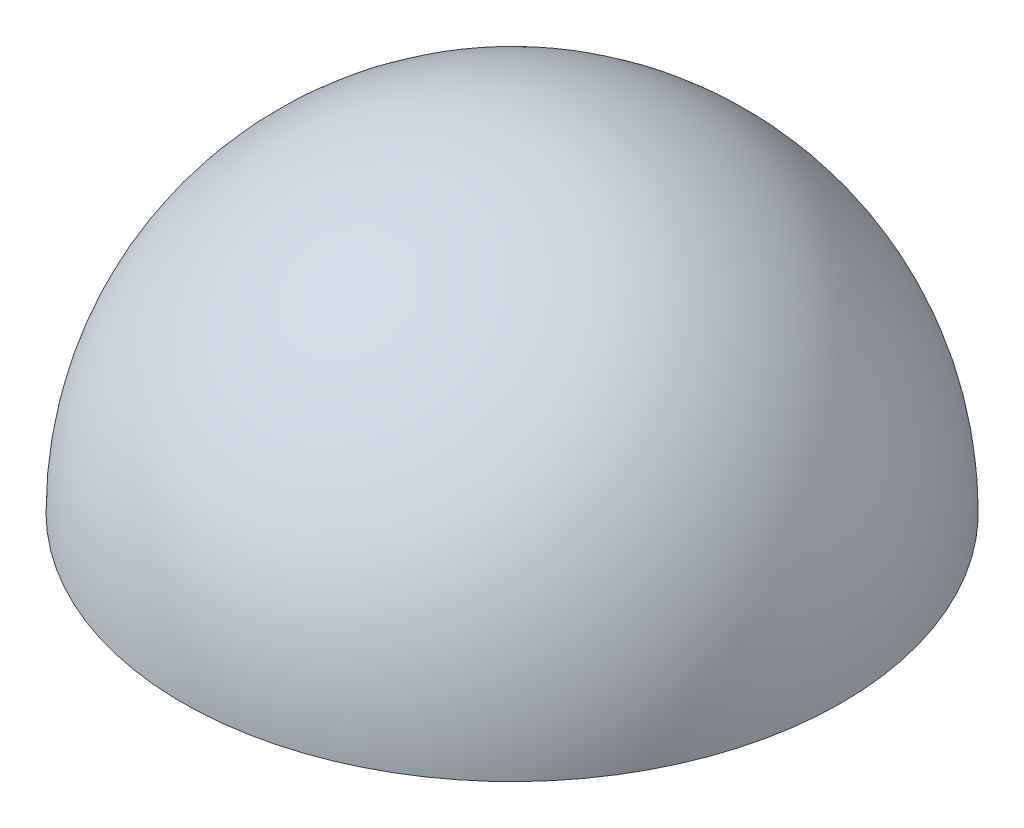
SolidWorks part; units mm, degrees
ref_plane "Front Plane" through (0, 0, 0) normal (0, 0, 1) x (1, 0, 0)
ref_plane "Top Plane" through (0, 0, 0) normal (0, 1, 0) x (1, 0, 0)
ref_plane "Right Plane" through (0, 0, 0) normal (1, 0, 0) x (0, 0, -1)
sketch "Sketch1" plane through (0, 0, 0) normal (0, 1, 0) x (1, 0, 0)
  line L0 (-19.7227, 26.8438) -> (-8.6611, -8.9876)
  circle A0 centre (-14.1919, 8.9281) radius 18.75
  dimension "D1" = 37.5
revolve "Revolve1" add sketch "Sketch1" angle 180 about L0 region at (-21.7955, 0, -6.5807) reverse direction yes
